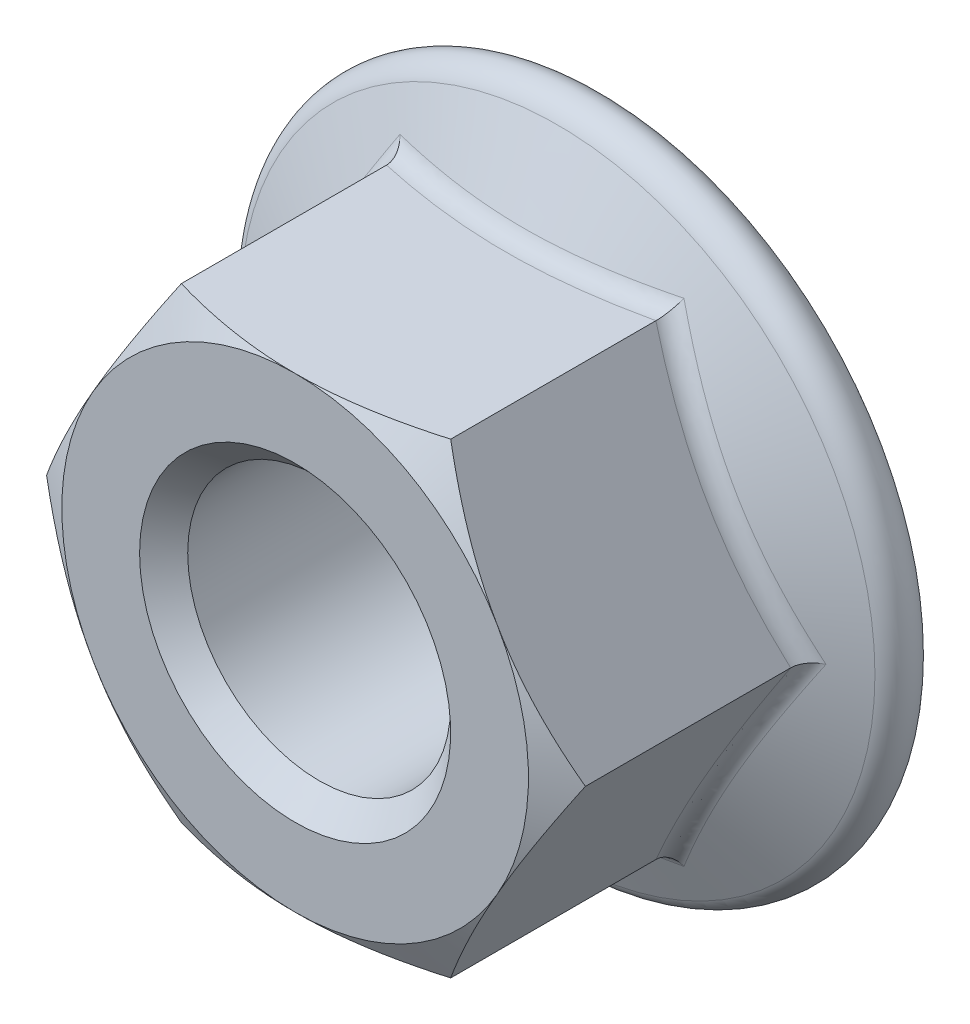
SolidWorks part; units mm, degrees
ref_plane "Front" through (0, 0, 0) normal (0, 0, 1) x (1, 0, 0)
ref_plane "Top" through (0, 0, 0) normal (0, 1, 0) x (1, 0, 0)
ref_plane "Right" through (0, 0, 0) normal (1, 0, 0) x (0, 0, -1)
sketch "Sketch1" plane through (0, 0, 0) normal (0, 0, 1) x (1, 0, 0)
  line L1 (6.0622, -10.5) -> (12.1244, 0)
  line L2 (12.1244, 0) -> (6.0622, 10.5)
  line L3 (6.0622, 10.5) -> (-6.0622, 10.5)
  line L4 (-6.0622, 10.5) -> (-12.1244, 0)
  line L5 (-12.1244, 0) -> (-6.0622, -10.5)
  line L6 (-6.0622, -10.5) -> (6.0622, -10.5)
  circle A0 centre (0, 0) radius 10.5 construction
  circle A1 centre (0, 0) radius 5.9175
  dimension "D1" = 11.835
extrude "BaseNut" add sketch "Sketch1" against normal blind 14
cosmetic thread "ThreadCosmetic1" parameters "D2"=14
sketch "Sketch3" plane through (0.6779, 0, -16.6426) normal (0, 1, 0) x (0, 0, -1)
  line L0 (4.0352, 0.6779) -> (-19.0613, 0.6779) construction
  line L2 (-16.6426, 11.1779) -> (-15.7048, 12.8022)
  line L4 (-15.7048, 12.8022) -> (-16.6426, 12.8022)
  line L5 (-16.6426, 12.8022) -> (-16.6426, 11.1779)
  line L6 (-9.6426, 12.8022) -> (-9.6426, 14.238) construction
  line L8 (-2.6426, 12.8022) -> (-2.6426, 11.1779)
  line L9 (-3.5805, 12.8022) -> (-2.6426, 12.8022)
  line L10 (-2.6426, 11.1779) -> (-3.5805, 12.8022)
  line L11 (-2.6426, 12.8022) -> (-16.6426, 12.8022) construction
  dimension "D1" = 30
revolve "Double-Chamfer" cut sketch "Sketch3" angle 360 about L0
sketch "Sketch4" plane through (4.6827, 0, -16.7173) normal (0, 1, 0) x (0, 0, -1)
  line L0 (-21.7744, 4.6827) -> (9.7398, 4.6827) construction
  line L2 (-8.8119, 30.5008) -> (-8.8119, 8.9315) construction
  line L3 (-4.9096, 18.9687) -> (-8.8119, 10.6002)
  line L4 (-2.7173, 10.6002) -> (-16.7173, 10.6002) construction
  line L5 (-2.7173, 10.6002) -> (-2.7173, 18.4827)
  line L11 (-8.8119, 10.6002) -> (-2.7173, 10.6002)
  arc A0 (-2.7173, 18.4827) -> (-4.9096, 18.9687) centre (-3.8673, 18.4827) ccw
  dimension "dc" = 29.9
  dimension "m1" = 14
revolve "Flange" add sketch "Sketch4" angle 360 about L0
fillet "FlangeFillet" radius 0.9 6 edges at (-7.683, -7.6927, -10.2159) (-10.5036, 2.8073, -10.2159) (7.683, 7.6927, -10.2159) (10.5036, -2.8073, -10.2159)
sketch "Sketch5" plane through (-5.1971, 0, -15.1971) normal (0, 1, 0) x (0, 0, -1)
  line L0 (3.5984, -5.1971) -> (-23.9926, -5.1971) construction
  line L1 (-1.1971, 0.7204) -> (-15.1971, 0.7204) construction
  line L2 (-15.1971, 1.8029) -> (-15.1971, 0.7204)
  line L4 (-15.1971, 0.7204) -> (-14.1146, 0.7204)
  line L6 (-14.1146, 0.7204) -> (-15.1971, 1.8029)
  line L7 (-8.1971, 0.7204) -> (-8.1971, 0.9419) construction
  line L8 (-2.2796, 0.7204) -> (-1.1971, 1.8029)
  line L9 (-1.1971, 0.7204) -> (-2.2796, 0.7204)
  line L10 (-1.1971, 1.8029) -> (-1.1971, 0.7204)
  dimension "da" = 14
  dimension "D2" = 45
revolve "Hole" cut sketch "Sketch5" angle 360 about L0
sketch "Sketch6" plane through (0, 0, 0) normal (0, 1, 0) x (1, 0, 0)
  line L0 (-6.855, 1.0825) -> (-5.9175, 0.5413)
  line L1 (-5.9175, 0.5413) -> (-4.835, 0.5413)
  line L2 (-4.835, 0.5413) -> (-4.835, 1.6238)
  line L3 (-4.835, 1.6238) -> (-5.9175, 1.6238)
  line L4 (-5.9175, 1.6238) -> (-6.855, 1.0825)
  line L5 (0, 7.348) -> (0, 34.1252) construction
  dimension "D1" = 1.0825
  dimension "D2" = 11.835
revolve "Cut-Revolve10" [suppressed] cut sketch "Sketch6" angle 360 about L5
pattern_linear "LPattern10" [suppressed] count 11 spacing 1.299 along (0, 0, -1) of bodies 105
equation "\"m1@Sketch4\" = \"m@BaseNut\""
equation "\"sq@Sketch3\" = \"s@Sketch1\""
equation "\"D2@Sketch6\"=\"D1@Sketch1\""
equation "\"D1@Sketch6\"= (\"D2@ThreadCosmetic1\"  - \"D2@Sketch6\" )  / 2"
equation "\"D3@LPattern10\"=\"D1@Sketch6\" * 1.2 "
equation "\"D1@LPattern10\"=\"m@BaseNut\"  / \"D3@LPattern10\""
